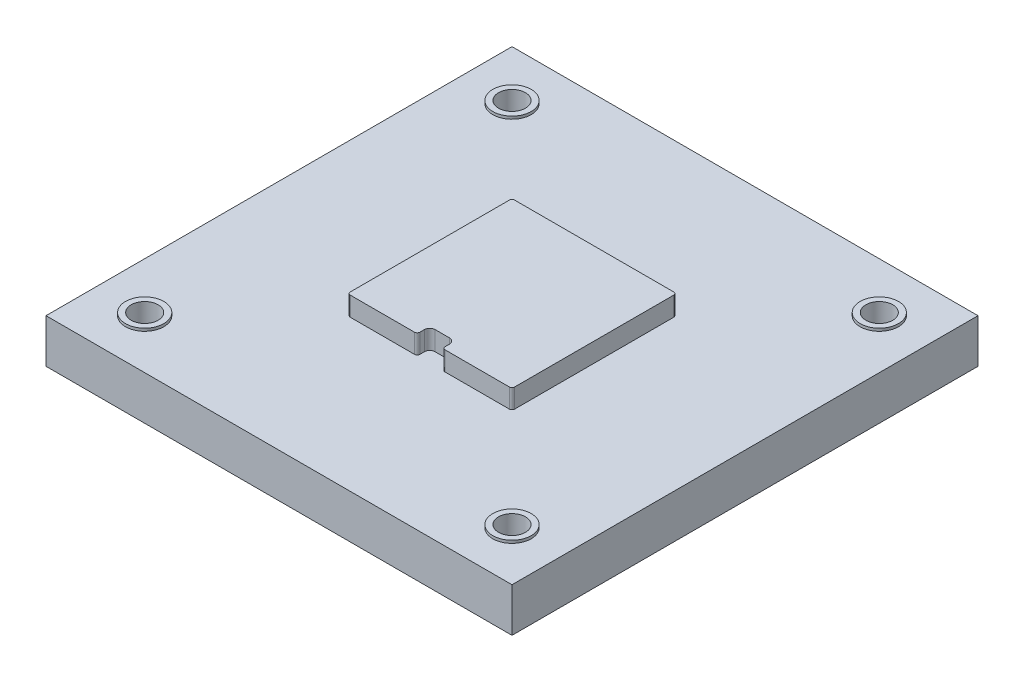
SolidWorks part; units mm, degrees
ref_plane "Front Plane" through (0, 0, 0) normal (0, 0, 1) x (1, 0, 0)
ref_plane "Top Plane" through (0, 0, 0) normal (0, 1, 0) x (1, 0, 0)
ref_plane "Right Plane" through (0, 0, 0) normal (1, 0, 0) x (0, 0, -1)
sketch "Sketch1" plane through (0, 0, 0) normal (0, 1, 0) x (1, 0, 0)
  line L0 (-71.3469, 0) -> (71.3469, 0) construction
  line L1 (-42.5, 42.5) -> (42.5, 42.5)
  line L2 (-42.5, 42.5) -> (-42.5, -42.5)
  line L3 (-42.5, -42.5) -> (42.5, -42.5)
  line L4 (42.5, 42.5) -> (42.5, -42.5)
  line L5 (-42.5, 42.5) -> (42.5, -42.5) construction
  line L6 (-42.5, -42.5) -> (42.5, 42.5) construction
  line L7 (0, -59.0713) -> (0, 59.0713) construction
  circle A0 centre (-33.5, 33.5) radius 2.4575
  circle A1 centre (-33.5, -33.5) radius 2.4575
  circle A2 centre (33.5, -33.5) radius 2.4575
  circle A3 centre (33.5, 33.5) radius 2.4575
  point P0 (0, 0)
  dimension "D3" = 4.915
  dimension "D1" = 85
  dimension "D2" = 85
  dimension "D4" = 9
  dimension "D5" = 9
extrude "Boss-Extrude1" add sketch "Sketch1" along normal blind 8
sketch "Sketch2" plane through (0, 0, 0) normal (0, -1, 0) x (1, 0, 0)
  line L0 (0, -4.4) -> (0, 4.4) construction
  line L1 (4.4, 0) -> (-4.4, 0) construction
  circle A0 centre (-33.5, 33.5) radius 3.969
  circle A1 centre (33.5, 33.5) radius 3.969
  circle A2 centre (33.5, -33.5) radius 3.969
  circle A3 centre (-33.5, -33.5) radius 3.969
  dimension "D1" = 7.938
extrude "Cut-Extrude1" cut sketch "Sketch2" against normal blind 4.166
sketch "Sketch3" plane through (0, 8, 0) normal (0, 1, 0) x (1, 0, 0)
  line L0 (0, -4.4) -> (0, 4.4) construction
  line L1 (-4.4, 0) -> (4.4, 0) construction
  circle A0 centre (33.5, -33.5) radius 3.5
  circle A1 centre (33.5, -33.5) radius 2.4575
  circle A2 centre (33.5, -33.5) radius 2.4575 construction
  circle A3 centre (-33.5, -33.5) radius 2.4575
  circle A4 centre (-33.5, -33.5) radius 3.5
  circle A5 centre (-33.5, 33.5) radius 3.5
  circle A6 centre (-33.5, 33.5) radius 2.4575
  circle A7 centre (33.5, 33.5) radius 2.4575
  circle A8 centre (33.5, 33.5) radius 3.5
  dimension "D1" = 7
extrude "Boss-Extrude2" add sketch "Sketch3" along normal blind 0.5
sketch "Sketch4" plane through (0, 8, 0) normal (0, 1, 0) x (1, 0, 0)
  line L0 (2.2929, -14.5) -> (2.2929, -13.7071)
  line L1 (14.5, -15) -> (2.7929, -15)
  line L2 (15, -14.5) -> (15, 14.5)
  line L3 (14.5, 15) -> (-14.5, 15)
  line L4 (-15, -14.5) -> (-15, 14.5)
  line L5 (15, -15) -> (-15, 15) construction
  line L6 (15, 15) -> (-15, -15) construction
  line L7 (1.2929, -12.7071) -> (-1.2929, -12.7071)
  line L8 (-2.2929, -13.7071) -> (-2.2929, -14.5)
  line L9 (-2.7929, -15) -> (-14.5, -15)
  arc A0 (-14.5, 15) -> (-15, 14.5) centre (-14.5, 14.5) ccw
  arc A1 (15, 14.5) -> (14.5, 15) centre (14.5, 14.5) ccw
  arc A2 (-14.5, -15) -> (-15, -14.5) centre (-14.5, -14.5) cw
  arc A3 (14.5, -15) -> (15, -14.5) centre (14.5, -14.5) ccw
  arc A4 (-2.2929, -14.5) -> (-2.7929, -15) centre (-2.7929, -14.5) cw
  arc A5 (2.2929, -14.5) -> (2.7929, -15) centre (2.7929, -14.5) ccw
  arc A6 (-1.2929, -12.7071) -> (-2.2929, -13.7071) centre (-1.2929, -13.7071) ccw
  arc A7 (2.2929, -13.7071) -> (1.2929, -12.7071) centre (1.2929, -13.7071) ccw
  point P0 (0, 0)
  point P10 (0, -12.7071)
  point P25 (-2.2929, -15)
  point P30 (-2.2929, -12.7071)
  point P33 (2.2929, -12.7071)
  dimension "D4" = 0.5
  dimension "D6" = 0.5
  dimension "D7" = 1
  dimension "D1" = 30
  dimension "D2" = 2.2929
  dimension "D3" = 4.5858
  dimension "D5" = 30
extrude "Boss-Extrude3" add sketch "Sketch4" along normal blind 3.5
